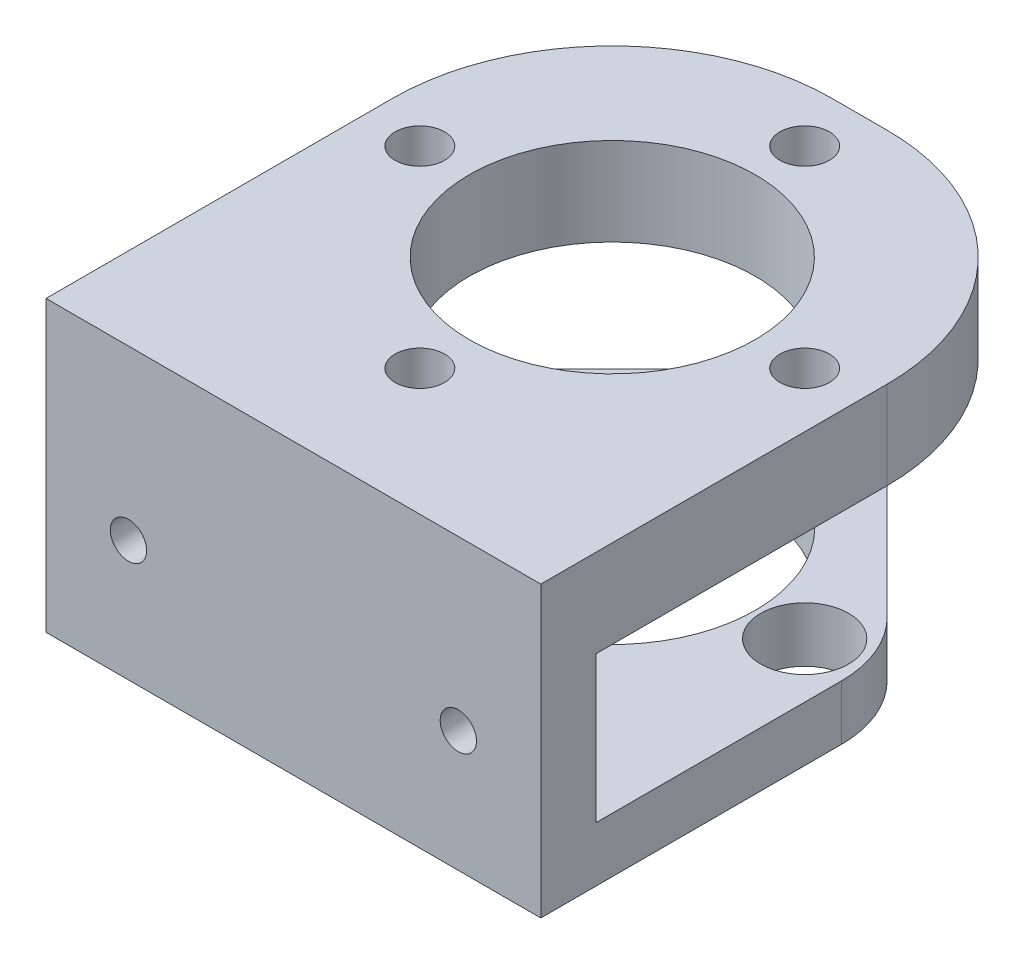
SolidWorks part; units mm, degrees
ref_plane "前视基准面" through (0, 0, 0) normal (0, 0, 1) x (1, 0, 0)
ref_plane "上视基准面" through (0, 0, 0) normal (0, 1, 0) x (1, 0, 0)
ref_plane "右视基准面" through (0, 0, 0) normal (1, 0, 0) x (0, 0, -1)
sketch "草图1" plane through (0, 0, 0) normal (0, 1, 0) x (1, 0, 0)
  line L5 (-22.5, -22.5) -> (22.5, -22.5)
  line L6 (-22.5, -22.5) -> (-22.5, 22.5)
  line L7 (-22.5, 22.5) -> (22.5, 22.5)
  line L8 (22.5, -22.5) -> (22.5, 22.5)
  line L9 (-22.5, -22.5) -> (22.5, 22.5) construction
  line L10 (-22.5, 22.5) -> (22.5, -22.5) construction
  circle A0 centre (0, 0) radius 13
  point P0 (0, 0)
  dimension "D1" = 26
  dimension "D2" = 45
  dimension "D3" = 45
extrude "凸台-拉伸1" add sketch "草图1" along normal blind 8
fillet "圆角1" radius 20 2 edges at (22.5, 4, -22.5) (-22.5, 4, -22.5)
sketch "草图2" plane through (0, 0, 22.5) normal (0, 0, 1) x (1, 0, 0)
  line L2 (-22.5, 0) -> (22.5, 0)
  line L3 (-22.5, 0) -> (-22.5, 8)
  line L4 (-22.5, 8) -> (22.5, 8)
  line L5 (22.5, 0) -> (22.5, 8)
extrude "凸台-拉伸2" add sketch "草图2" along normal blind 6.5
hole_wizard "M5 螺纹孔的螺纹孔钻头1" [suppressed] positions "草图4" profile "草图3" hole size "M5" standard "ISO"
sketch "草图4" plane through (0, 0, 29) normal (0, 0, 1) x (1, 0, 0)
  line L0 (0, 0) -> (0, 8) construction
  line L1 (-22.5, 0) -> (22.5, 0) construction
  line L2 (22.5, 8) -> (-22.5, 8) construction
  point P1 (-15, 4)
  point P3 (15, 4)
  dimension "D1" = 30
  dimension "D2" = 4
sketch "草图3" plane through (-15, 4, 29) normal (1, 0, 0) x (0, -1, 0)
  line L0 (0, 0) -> (0, 21.2618)
  line L1 (0, 21.2618) -> (2.1, 20)
  line L2 (2.1, 20) -> (2.1, 0)
  line L5 (2.1, 0) -> (0, 0)
  line L10 (0, 21.2618) -> (-2.1, 20) construction
  line L11 (0, -6.35) -> (0, 107.95) construction
  dimension "孔直径" = 4.2
  dimension "孔深度" = 20
  dimension "导头角度" = 118
hole_wizard "M4 六角凹头螺钉的柱形沉头孔1" positions "草图5" profile "草图6" counterbore size "M4" standard "ISO"
sketch "草图5" plane through (0, 0, 0) normal (0, -1, 0) x (-1, 0, 0)
  point P0 (0, -17.5)
  dimension "D1" = 17.5
sketch "草图6" plane through (0, 0, 17.5) normal (1, 0, 0) x (0, 0, -1)
  line L0 (0, 0) -> (0, 21.3519)
  line L1 (0, 21.3519) -> (2.25, 20)
  line L2 (2.25, 20) -> (2.25, 4.4)
  line L3 (2.25, 4.4) -> (4, 4.4)
  line L4 (4, 4.4) -> (4, 0)
  line L5 (4, 0) -> (0, 0)
  line L10 (0, 21.3519) -> (-2.25, 20) construction
  line L11 (0, -6.35) -> (0, 107.95) construction
  dimension "孔直径" = 4.5
  dimension "孔深度" = 20
  dimension "柱形沉头孔直径" = 8
  dimension "柱形沉头孔深度" = 4.4
  dimension "导头角度" = 118
pattern_circular "阵列(圆周)1" count 4 over 360 about axis through (0, 0, 0) along (0, 1, 0) of "M4 六角凹头螺钉的柱形沉头孔1"
sketch "草图7" plane through (0, 0, 0) normal (0, -1, 0) x (1, 0, 0)
  line L0 (22.5, 29) -> (22.5, -2.5) construction
  line L1 (-22.5, 29) -> (22.5, 29)
  line L2 (-22.5, 29) -> (-22.5, 24)
  line L3 (-22.5, 24) -> (22.5, 24)
  line L4 (22.5, 29) -> (22.5, 24)
  dimension "D1" = 5
extrude "凸台-拉伸3" add sketch "草图7" along normal blind 13.3
sketch "草图9" plane through (0, 0, 29) normal (0, 0, 1) x (1, 0, 0)
  line L1 (-22.5, -13.3) -> (22.5, -13.3)
  line L2 (-22.5, -13.3) -> (-22.5, -18.3)
  line L3 (-22.5, -18.3) -> (22.5, -18.3)
  line L4 (22.5, -13.3) -> (22.5, -18.3)
  dimension "D1" = 5
extrude "凸台-拉伸4" add sketch "草图9" against normal blind 51.5
sketch "草图10" plane through (0, -13.3, 0) normal (0, 1, 0) x (1, 0, 0)
  circle A0 centre (0, 0) radius 13.025
  dimension "D1" = 26.05
extrude "切除-拉伸1" cut sketch "草图10" against normal blind 53.3
sketch "草图11" plane through (0, -18.3, 0) normal (0, -1, 0) x (-1, 0, 0)
  circle A0 centre (0, -17.5) radius 4
  circle A1 centre (-17.5, 0) radius 4
  circle A2 centre (0, 17.5) radius 4
  circle A3 centre (17.5, 0) radius 4
  point P12 (0, 0)
  dimension "D2" = 8
  dimension "D1" = 17.5
  dimension "D3" = 4
extrude "切除-拉伸2" cut sketch "草图11" against normal up to next
hole_wizard "M4 螺纹孔的螺纹孔钻头1" [suppressed] positions "草图16" profile "草图17" hole size "M4" standard "ISO"
sketch "草图16" plane through (0, 0, 29) normal (0, 0, 1) x (1, 0, 0)
  line L0 (-22.5, -18.3) -> (22.5, -18.3) construction
  line L1 (0, -1000.3996) -> (0, 48999.6004) construction
  point P0 (-15, -16.3)
  point P2 (15, -16.3)
  dimension "D1" = 30
  dimension "D2" = 2
sketch "草图17" plane through (-15, -16.3, 29) normal (1, 0, 0) x (0, -1, 0)
  line L0 (0, 0) -> (0, 20.9914)
  line L1 (0, 20.9914) -> (1.65, 20)
  line L2 (1.65, 20) -> (1.65, 0)
  line L5 (1.65, 0) -> (0, 0)
  line L10 (0, 20.9914) -> (-1.65, 20) construction
  line L11 (0, -6.35) -> (0, 107.95) construction
  dimension "孔直径" = 3.3
  dimension "孔深度" = 20
  dimension "导头角度" = 118
fillet "圆角3" [suppressed] radius 20
sketch "草图18" plane through (0, 0, 24) normal (0, 0, -1) x (-1, 0, 0)
  line L0 (-22.5, -13.3) -> (-22.5, 0) construction
  line L1 (22.5, -13.3) -> (22.5, 0) construction
  line L2 (22.5, -13.3) -> (-22.5, -13.3) construction
  point P0 (-15, -7.3)
  point P1 (15, -7.3)
  dimension "D1" = 7.5
  dimension "D2" = 7.5
  dimension "D3" = 6
hole_wizard "M4 螺纹孔1" positions "3D草图1" profile "草图19" tap size "M4" standard "ISO"
sketch3d "3D草图1"
  point P0 (15, -7.3, 24)
  point P3 (-15, -7.3, 24)
sketch "草图19" plane through (15, -7.3, 24) normal (1, 0, 0) x (0, 1, 0)
  line L0 (0, 0) -> (0, 12.4914)
  line L1 (0, 12.4914) -> (1.65, 11.5)
  line L2 (1.65, 11.5) -> (1.65, 0)
  line L5 (1.65, 0) -> (0, 0)
  line L10 (0, 12.4914) -> (-1.65, 11.5) construction
  line L11 (0, -6.35) -> (0, 107.95) construction
  dimension "螺纹孔钻头直径" = 3.3
  dimension "螺纹孔钻头深度" = 11.5
  dimension "导头角度" = 118
cosmetic thread "孔螺蚊线1" parameters "D1"=5, "D2"=4
cosmetic thread "孔螺蚊线2" parameters "D1"=5, "D2"=4
sketch "草图23" plane through (0, -18.3, 0) normal (0, -1, 0) x (1, 0, 0)
  line L0 (-22.5, -2.5) -> (-2.5, -22.5)
  line L1 (-22.5, -22.5) -> (-22.5, 29) construction
  line L2 (-22.5, -22.5) -> (22.5, -22.5) construction
  line L3 (-2.5, -22.5) -> (-22.5, -22.5)
  line L4 (-22.5, -22.5) -> (-22.5, -2.5)
  line L5 (22.5, -22.5) -> (22.5, -2.5)
  line L6 (22.5, -22.5) -> (22.5, 29) construction
  line L7 (22.5, -2.5) -> (2.5, -22.5)
  line L8 (2.5, -22.5) -> (22.5, -22.5)
  dimension "D1" = 20
  dimension "D2" = 20
  dimension "D3" = 20
  dimension "D4" = 20
extrude "切除-拉伸3" cut sketch "草图23" against normal up to next
fillet "圆角4" radius 10 4 edges at (-22.5, -15.8, -2.5) (22.5, -15.8, -2.5) (2.5, -15.8, -22.5) (-2.5, -15.8, -22.5)
